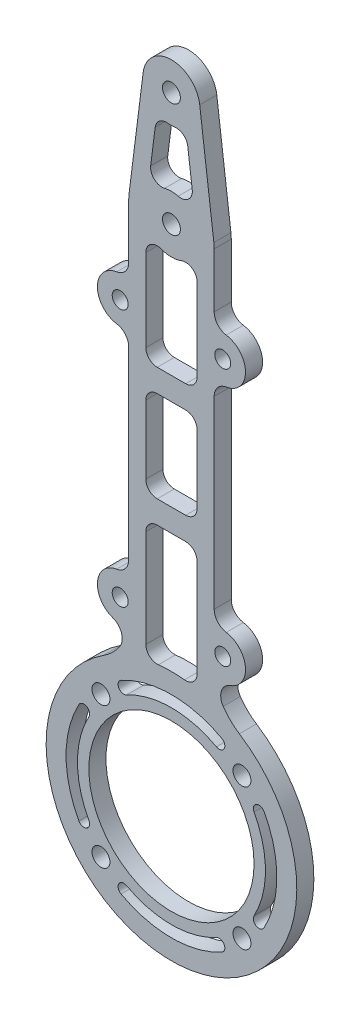
SolidWorks part; units mm, degrees
material "Thornel Mat VMA"
ref_plane "前视基准面" through (0, 0, 0) normal (0, 0, 1) x (1, 0, 0)
ref_plane "上视基准面" through (0, 0, 0) normal (0, 1, 0) x (1, 0, 0)
ref_plane "右视基准面" through (0, 0, 0) normal (1, 0, 0) x (0, 0, -1)
sketch "草图1" plane through (0, 0, 0) normal (0, 0, 1) x (1, 0, 0)
  line L0 (0, 0) -> (0, -50000) construction
  line L1 (-7.5, 0) -> (-7.5, -69.3179)
  line L2 (7.5, 0) -> (7.5, -69.3179)
  line L3 (-4.9608, 20.625) -> (-7.4412, 0.9375)
  line L4 (4.9608, 20.625) -> (7.4412, 0.9375)
  line L5 (0, -90) -> (50000, -90) construction
  line L6 (0, -90) -> (35355.3391, 35265.3391) construction
  line L7 (0, -90) -> (-35355.3391, 35265.3391) construction
  circle A0 centre (0, 0) radius 1.575
  circle A1 centre (0, -90) radius 22
  circle A2 centre (0, 0) radius 7.5
  circle A3 centre (0, 20) radius 1.575
  circle A4 centre (0, 20) radius 5
  circle A5 centre (0, -90) radius 14.5
  circle A6 centre (-12.3744, -77.6256) radius 1.575
  circle A7 centre (12.3744, -77.6256) radius 1.575
  circle A8 centre (12.3744, -102.3744) radius 1.575
  circle A9 centre (-12.3744, -102.3744) radius 1.575
  circle A10 centre (0, -90) radius 17.5 construction
  point P37 (0, -90)
  dimension "D1" = 3.15
  dimension "D2" = 44
  dimension "D4" = 3.15
  dimension "D6" = 15
  dimension "D7" = 10
  dimension "D8" = 29
  dimension "D10" = 3.15
  dimension "D3" = 90
  dimension "D5" = 20
  dimension "D9" = 45
  dimension "D11" = 35
  dimension "D12" = 4
extrude "凸台-拉伸1" add sketch "草图1" along normal blind 3 contours L0 A4 L3 A2 | L0 A4 A3 | A4 L0 A3 | A4 L0 A2 L4 | L0 A2 A0 | A2 L0 A0 | A2 L0 A1 L2 | L0 A2 L1 A1 | L0 A1 A5 | A1 L0 A5 region at (0, -37.141, 0) region at (-7.2736, 0.4564, 0) region at (0, -68.6223, 0) region at (0, 11.0094, 0) region at (0, 24.8586, 0)
sketch "草图2" plane through (0, 0, 3) normal (0, 0, 1) x (1, 0, 0)
  line L0 (0, 0) -> (0, -50000) construction
  line L1 (-2.5571, 15.7034) -> (-4.1923, 2.7249)
  line L2 (-4.9608, 20.625) -> (-7.4412, 0.9375) construction
  line L3 (-4.5, -68.4651) -> (-4.5, -2.1794)
  line L4 (-7.5, 0) -> (-7.5, -69.3179) construction
  line L5 (4.5, -68.4651) -> (4.5, -2.1794)
  line L6 (2.5571, 15.7034) -> (4.1923, 2.7249)
  circle A0 centre (0, 20) radius 5
  circle A1 centre (0, 0) radius 5
  circle A2 centre (0, -90) radius 22
  dimension "D1" = 10
  dimension "D2" = 10
  dimension "D3" = 3
  dimension "D4" = 3
extrude "切除-拉伸1" cut sketch "草图2" against normal blind 3 contours A0 L0 A1 L6 | L0 A0 L1 A1 | L0 A1 L3 A2 | A1 L0 A2 L5 region at (2.2677, -36.1727, 3) region at (-2.2677, -36.1727, 3) region at (0, 9.4049, 3)
sketch "草图3" plane through (0, 0, 3) normal (0, 0, 1) x (1, 0, 0)
  line L0 (-4.5, -25) -> (4.5, -25) construction
  line L5 (-4.5, -68.4651) -> (-4.5, -2.1794) construction
  line L6 (4.5, -68.4651) -> (4.5, -2.1794) construction
  line L7 (-4.5, -45) -> (4.5, -45) construction
  line L8 (-4.5, -47) -> (4.5, -47)
  line L9 (-4.5, -43) -> (4.5, -43)
  line L10 (-4.5, -27) -> (4.5, -27)
  line L11 (-4.5, -23) -> (4.5, -23)
  line L12 (-4.5, -23) -> (-4.5, -27)
  line L13 (4.5, -23) -> (4.5, -27)
  line L14 (-4.5, -43) -> (-4.5, -47)
  line L15 (4.5, -43) -> (4.5, -47)
  dimension "D1" = 2
  dimension "D5" = 25
  dimension "D6" = 20
  dimension "D2" = 2
  dimension "D3" = 2
  dimension "D4" = 2
extrude "凸台-拉伸2" add sketch "草图3" against normal up to surface (3 mm away) up to face at (0, -35.9111, 0)
sketch "草图4" plane through (0, 0, 3) normal (0, 0, 1) x (1, 0, 0)
  line L0 (0, 0) -> (0, -50000) construction
  circle A0 centre (-9, -16) radius 1.4
  circle A1 centre (-9, -61.2) radius 1.4
  circle A2 centre (-9, -16) radius 4
  circle A3 centre (-9, -61.2) radius 4
  circle A4 centre (9, -61.2) radius 4
  circle A5 centre (9, -16) radius 4
  circle A6 centre (9, -61.2) radius 1.4
  circle A7 centre (9, -16) radius 1.4
  dimension "D3" = 2.8
  dimension "D5" = 8
  dimension "D1" = 45.2
  dimension "D2" = 18
  dimension "D4" = 16
extrude "凸台-拉伸3" add sketch "草图4" against normal up to surface (3 mm away) up to face at (0, -13.2949, 0)
fillet "圆角1" radius 2 16 edges at (2.5571, 15.7034, 1.5) (4.1923, 2.7249, 1.5) (-4.1923, 2.7249, 1.5) (-2.5571, 15.7034, 1.5) (-4.5, -68.4651, 1.5) (-4.5, -47, 1.5) (4.5, -47, 1.5) (4.5, -68.4651, 1.5) (-4.5, -27, 1.5) (4.5, -27, 1.5) (4.5, -43, 1.5) (-4.5, -43, 1.5) (4.5, -2.1794, 1.5) (4.5, -23, 1.5) (-4.5, -23, 1.5) (-4.5, -2.1794, 1.5)
fillet "圆角2" radius 10 2 edges at (-7.5, -69.3179, 1.5) (7.5, -69.3179, 1.5)
fillet "圆角3" radius 2.5 8 edges at (7.5, -57.4919, 1.5) (7.5, -64.9081, 1.5) (-7.5, -64.9081, 1.5) (-7.5, -57.4919, 1.5) (-7.5, -12.2919, 1.5) (7.5, -12.2919, 1.5) (7.5, -19.7081, 1.5) (-7.5, -19.7081, 1.5)
sketch "草图5" plane through (0, 0, 3) normal (0, 0, 1) x (1, 0, 0)
  arc A0 (9.2342, -75.1346) -> (-9.2342, -75.1346) centre (0, -90) ccw construction
  arc A1 (8.8483, -73.7532) -> (-8.8483, -73.7532) centre (0, -90) ccw
  arc A2 (7.8917, -75.5096) -> (-7.8917, -75.5096) centre (0, -90) ccw
  arc A3 (-8.8483, -73.7532) -> (-7.8917, -75.5096) centre (-8.37, -74.6314) ccw
  arc A4 (7.8917, -75.5096) -> (8.8483, -73.7532) centre (8.37, -74.6314) ccw
  circle A5 centre (-12.3744, -77.6256) radius 1.575 construction
  circle A6 centre (12.3744, -77.6256) radius 1.575 construction
  arc A7 (16.2468, -81.1517) -> (14.4904, -82.1083) centre (15.3686, -81.63) ccw
  arc A8 (14.4904, -97.8917) -> (14.4904, -82.1083) centre (0, -90) ccw
  arc A9 (14.4904, -97.8917) -> (16.2468, -98.8483) centre (15.3686, -98.37) ccw
  arc A10 (16.2468, -98.8483) -> (16.2468, -81.1517) centre (0, -90) ccw
  arc A11 (8.8483, -106.2468) -> (7.8917, -104.4904) centre (8.37, -105.3686) ccw
  arc A12 (-7.8917, -104.4904) -> (7.8917, -104.4904) centre (0, -90) ccw
  arc A13 (-7.8917, -104.4904) -> (-8.8483, -106.2468) centre (-8.37, -105.3686) ccw
  arc A14 (-8.8483, -106.2468) -> (8.8483, -106.2468) centre (0, -90) ccw
  arc A15 (-16.2468, -98.8483) -> (-14.4904, -97.8917) centre (-15.3686, -98.37) ccw
  arc A16 (-14.4904, -82.1083) -> (-14.4904, -97.8917) centre (0, -90) ccw
  arc A17 (-14.4904, -82.1083) -> (-16.2468, -81.1517) centre (-15.3686, -81.63) ccw
  arc A18 (-16.2468, -81.1517) -> (-16.2468, -98.8483) centre (0, -90) ccw
  point P36 (0, -90)
  dimension "D1" = 1
  dimension "D2" = 1
  dimension "D4" = 5
  dimension "D3" = 5
  dimension "D5" = 4
extrude "切除-拉伸2" cut sketch "草图5" against normal blind 10
